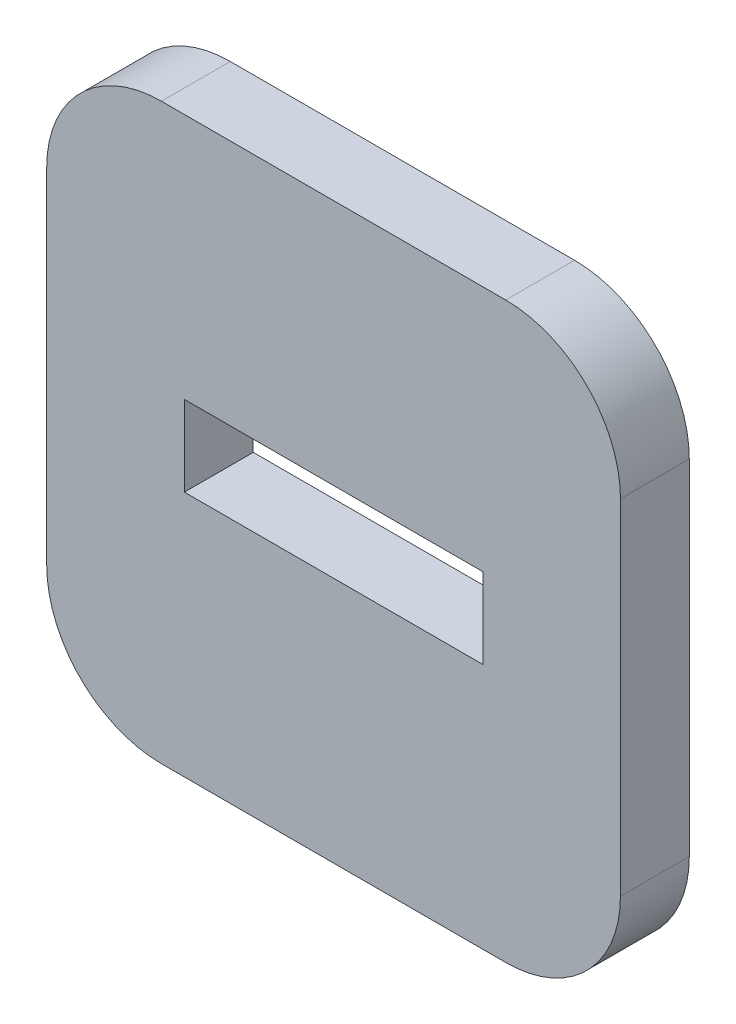
SolidWorks part; units mm, degrees
ref_plane "Front Plane" through (0, 0, 0) normal (0, 0, 1) x (1, 0, 0)
ref_plane "Top Plane" through (0, 0, 0) normal (0, 1, 0) x (1, 0, 0)
ref_plane "Right Plane" through (0, 0, 0) normal (1, 0, 0) x (0, 0, -1)
sketch "Sketch1" plane through (0, 0, 0) normal (0, 0, 1) x (1, 0, 0)
  line L0 (-1135.7574, 0) -> (48864.2426, 0) construction
  line L1 (-135.7574, -1000.0105) -> (-135.7574, 48999.9895) construction
  line L11 (-148.4574, -12.7) -> (-123.0574, -12.7)
  line L12 (-148.4574, -12.7) -> (-148.4574, 12.7)
  line L13 (-148.4574, 12.7) -> (-123.0574, 12.7)
  line L14 (-129.1534, -1.778) -> (-129.1534, 1.778)
  line L15 (-129.1534, 1.778) -> (-142.3614, 1.778)
  line L16 (-142.3614, 1.778) -> (-142.3614, -1.778)
  line L17 (-142.3614, -1.778) -> (-129.1534, -1.778)
  line L18 (-129.1534, -1.778) -> (-129.1534, 1.778)
  line L19 (-129.1534, 1.778) -> (-142.3614, 1.778)
  line L20 (-142.3614, 1.778) -> (-142.3614, -1.778)
  line L21 (-142.3614, -1.778) -> (-129.1534, -1.778)
  line L22 (-123.0574, -12.7) -> (-123.0574, 12.7)
  line L23 (-148.4574, -12.7) -> (-123.0574, 12.7) construction
  line L24 (-148.4574, 12.7) -> (-123.0574, -12.7) construction
  point P0 (-135.7574, 0)
  point P7 (-135.7574, 1.778)
  dimension "D2" = 25.4
  dimension "D3" = 25.4
  dimension "D1" = 0.254
extrude "Boss-Extrude1" add sketch "Sketch1" against normal blind 3.048 contours L13 L22 L11 L12 | L19 L20 L21 L18
fillet "Fillet1" radius 5.08 4 edges at (-148.4574, -12.7, -1.524) (-123.0574, -12.7, -1.524) (-123.0574, 12.7, -1.524) (-148.4574, 12.7, -1.524)
